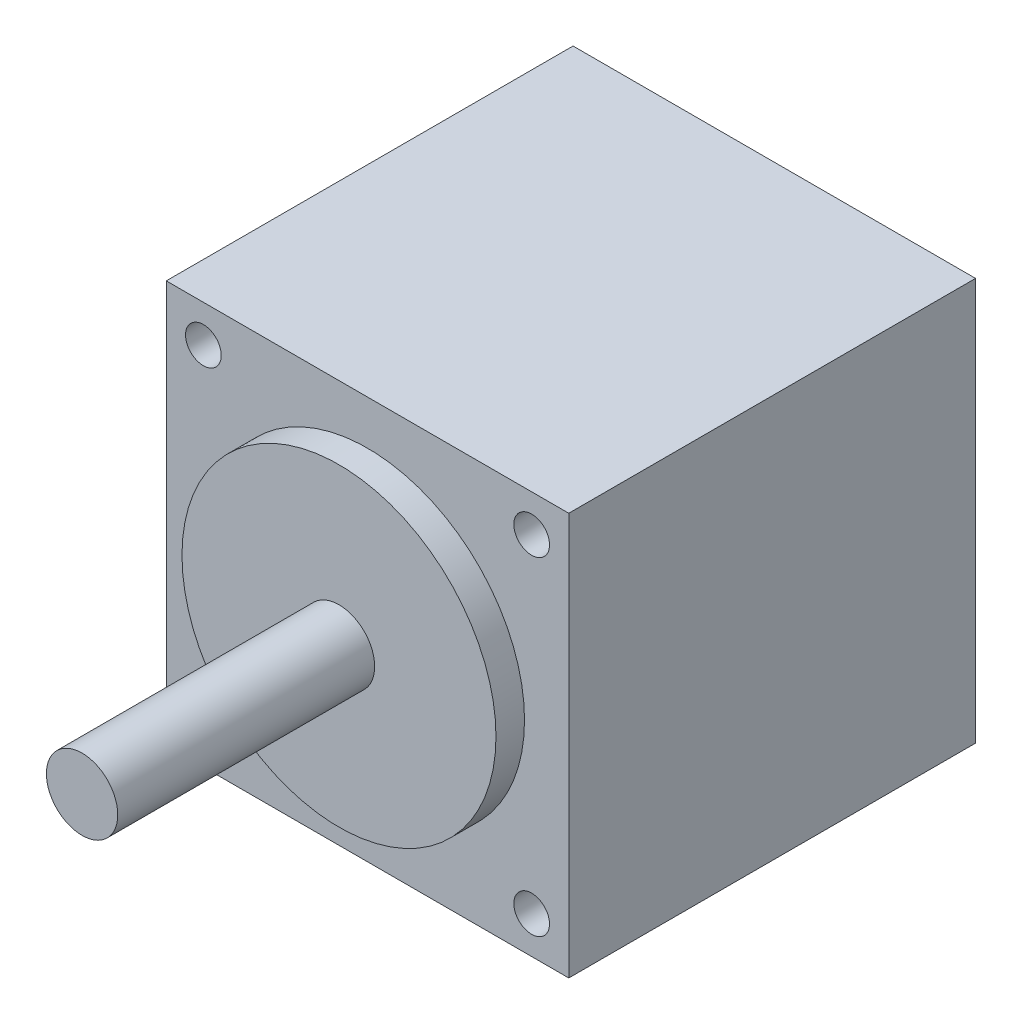
SolidWorks part; units mm, degrees
ref_plane "Front Plane" through (0, 0, 0) normal (0, 0, 1) x (1, 0, 0)
ref_plane "Top Plane" through (0, 0, 0) normal (0, 1, 0) x (1, 0, 0)
ref_plane "Right Plane" through (0, 0, 0) normal (1, 0, 0) x (0, 0, -1)
sketch "Sketch1" plane through (0, 0, 0) normal (0, 0, 1) x (1, 0, 0)
  line L1 (-14.1, 14.1) -> (14.1, 14.1)
  line L2 (-14.1, 14.1) -> (-14.1, -14.1)
  line L3 (-14.1, -14.1) -> (14.1, -14.1)
  line L4 (14.1, 14.1) -> (14.1, -14.1)
  circle A0 centre (0, 0) radius 2.5
  circle A1 centre (-11.5, 11.5) radius 1.25
  circle A2 centre (11.5, 11.5) radius 1.25
  circle A3 centre (11.5, -11.5) radius 1.25
  circle A4 centre (-11.5, -11.5) radius 1.25
  circle A5 centre (0, 0) radius 11
  point P8 (0, 14.1)
  point P10 (-14.1, 0)
  dimension "D1" = 5
  dimension "D8" = 2.5
  dimension "D9" = 22
  dimension "D2" = 28.2
  dimension "D3" = 28.2
  dimension "D4" = 11.5
  dimension "D5" = 11.5
  dimension "D6" = 2
  dimension "D7" = 2
extrude "Boss-Extrude1" add sketch "Sketch1" along normal blind 20 contours A0
extrude "Boss-Extrude2" add sketch "Sketch1<3>" along normal blind 2 contours A5
sketch "Sketch1<3>" plane through (0, 0, 0) normal (0, 0, 1) x (1, 0, 0) same geometry as "Sketch1"
extrude "Boss-Extrude3" add sketch "Sketch1<4>" against normal blind 28.5 separate body contours L4 L1 L2 L3 A5 A4 A3 A2 A1 region at (0, 13.7012, 0)
sketch "Sketch1<4>" plane through (0, 0, 0) normal (0, 0, 1) x (1, 0, 0) same geometry as "Sketch1"
